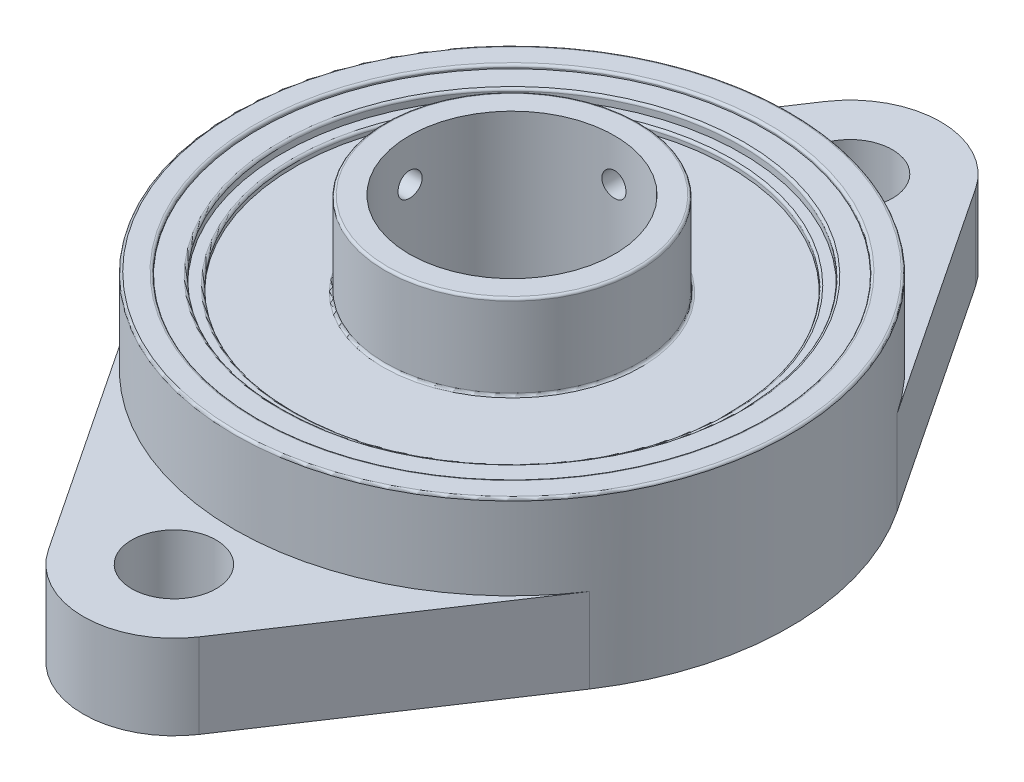
SolidWorks part; units mm, degrees
ref_plane "Front Plane" through (0, 0, 0) normal (0, 0, 1) x (1, 0, 0)
ref_plane "Top Plane" through (0, 0, 0) normal (0, 1, 0) x (1, 0, 0)
ref_plane "Right Plane" through (0, 0, 0) normal (1, 0, 0) x (0, 0, -1)
sketch "Sketch1" plane through (0, 0, 0) normal (0, 1, 0) x (1, 0, 0)
  line L0 (0, -35.5) -> (0, 35.5) construction
  line L1 (0, 0) -> (-50000, 0) construction
  line L2 (19.1544, -12.7321) -> (6.246, -32.1518)
  line L3 (19.1544, 12.7321) -> (6.246, 32.1518)
  line L4 (-19.1544, -12.7321) -> (-6.246, -32.1518)
  line L5 (-19.1544, 12.7321) -> (-6.246, 32.1518)
  circle A0 centre (0, 0) radius 23
  circle A1 centre (0, 0) radius 8.5
  circle A2 centre (0, 28) radius 3.5
  circle A3 centre (0, 0) radius 21
  circle A4 centre (0, 0) radius 10.5
  arc A5 (6.246, 32.1518) -> (-6.246, 32.1518) centre (0, 28) ccw
  circle A6 centre (0, -28) radius 3.5
  arc A7 (-6.246, -32.1518) -> (6.246, -32.1518) centre (0, -28) ccw
  circle A8 centre (0, 0) radius 19
  circle A9 centre (0, 0) radius 18
  point P6 (0, 0)
  dimension "D1" = 17
  dimension "D2" = 46
  dimension "D5" = 7
  dimension "D3" = 71
  dimension "D4" = 56
  dimension "D6" = 2
  dimension "D7" = 2
  dimension "D8" = 2
  dimension "D9" = 1
extrude "A1" add sketch "Sketch1" along normal blind 7 contours L4 A7 L2 A0 A6 | A0 A3 | L3 A5 L5 A0 A2 region at (12.3291, 0, 22.1953) region at (0, 0, 22.3495) region at (-12.3291, 0, -22.1953)
extrude "A" add sketch "Sketch1<3>" along normal blind 14 contours A0 A3 region at (0, 0, 22.3495)
sketch "Sketch1<3>" plane through (0, 0, 0) normal (0, 1, 0) x (1, 0, 0) same geometry as "Sketch1"
extrude "A0" add sketch "Sketch1<4>" along normal blind 19.5 contours A4 A1 region at (-10.203, 0, 0)
sketch "Sketch1<4>" plane through (0, 0, 0) normal (0, 1, 0) x (1, 0, 0) same geometry as "Sketch1"
extrude "Bearing outer d" add sketch "Sketch1<7>" along normal blind 11 from offset 2 separate body contours A8 A9 region at (-18.4626, 0, 0)
sketch "Sketch1<7>" plane through (0, 0, 0) normal (0, 1, 0) x (1, 0, 0) same geometry as "Sketch1"
extrude "Boss-Extrude6" add sketch "Sketch1<8>" along normal blind 12.5 from offset 1.2 contours A3 A8 region at (-20.406, 0, 0)
sketch "Sketch1<8>" plane through (0, 0, 0) normal (0, 1, 0) x (1, 0, 0) same geometry as "Sketch1"
extrude "Boss-Extrude7" add sketch "Sketch1<9>" along normal blind 11 from offset 1.5 contours A9 A4 region at (-17.4909, 0, 0)
sketch "Sketch1<9>" plane through (0, 0, 0) normal (0, 1, 0) x (1, 0, 0) same geometry as "Sketch1"
sketch "Sketch2" plane through (0, 0, 0) normal (1, 0, 0) x (0, 0, -1)
  line L0 (0, 0) -> (0, 50000) construction
  line L1 (-12.7321, 0) -> (12.7321, 0) construction
  line L2 (10.5, 16) -> (-10.5, 16) construction
  line L3 (10.5, 12.5) -> (10.5, 19.5) construction
  line L4 (-10.5, 19.5) -> (-10.5, 12.5) construction
  circle A0 centre (0, 16) radius 1
  point P4 (0, 0)
  dimension "D1" = 2
extrude "Cut-Extrude1" cut sketch "Sketch2" against normal up to next
sketch "Sketch3" plane through (0, 0, 0) normal (0, 0, 1) x (1, 0, 0)
  line L0 (0, 0) -> (0, 50000) construction
  line L1 (6, 16) -> (-49994, 16) construction
  line L3 (10.5, 12.5) -> (10.5, 19.5) construction
  circle A0 centre (0, 16) radius 1
  point P7 (10.5, 16)
  point P10 (0, 9.9)
  dimension "D1" = 2
extrude "Cut-Extrude2" cut sketch "Sketch3" against normal up to next
fillet "Fillet1" radius 0.2 1 edges at (0, 13, 18)
fillet "Fillet2" radius 0.2 5 edges at (0, 19.5, 10.5) (0, 12.5, 10.5) (0, 14, 23) (0, 14, 21) (0, 13.7, 19)
equation "\"A\"= \"D1@A\""
equation "\"A0\"= \"D1@A0\""
equation "\"A1\"= \"D1@A1\""
equation "\"D1@Bearing outer d\"=\"D1@Boss-Extrude6\" - 1.5"
equation "\"D1@Boss-Extrude6\"=\"D1@A\" - 1.5"
equation "\"D1@Boss-Extrude7\"= \"D1@Bearing outer d\""
equation "\"S\"= \"D19@Boss-Extrude7\""
equation "\"D19@Boss-Extrude6\"=\"D19@Boss-Extrude7\" - 0.3"
equation "\"H\"= \"D3@Sketch1\""
equation "\"J\"= \"D4@Sketch1\""
equation "\"L\"= \"D2@Sketch1\""
equation "\"N\"= \"D5@Sketch1\""
equation "\"d\"= \"D1@Sketch1\""
